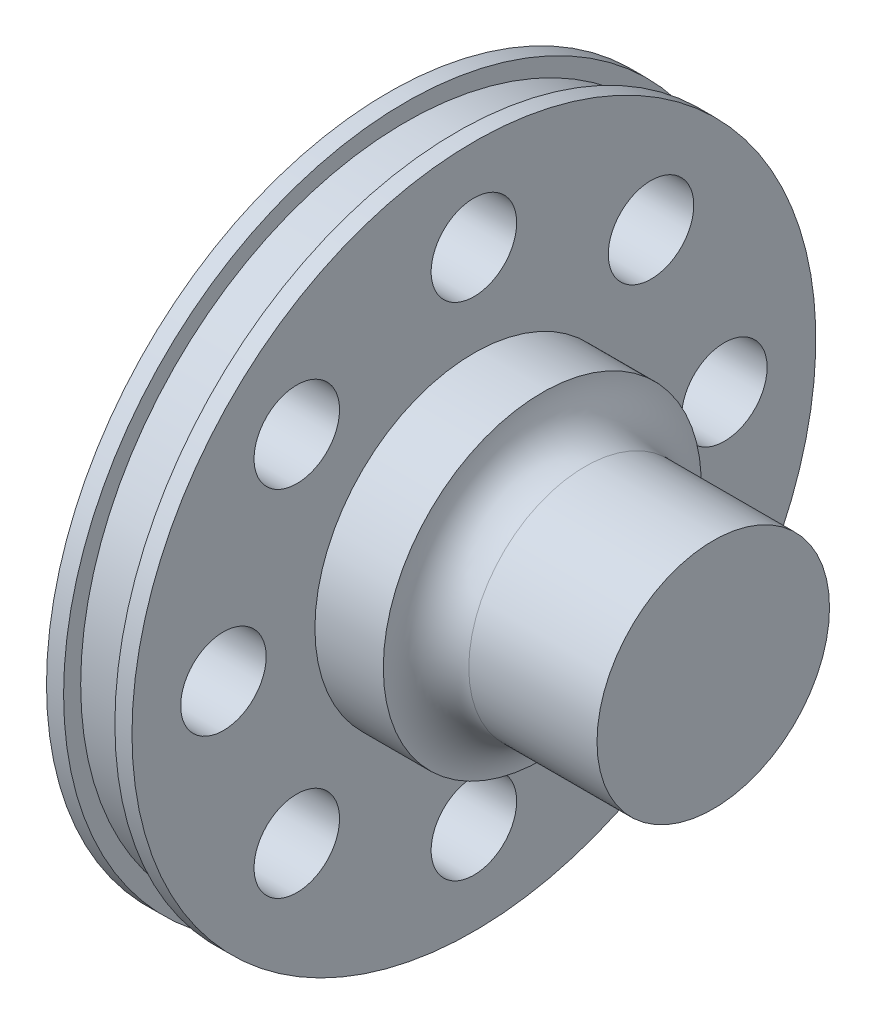
SolidWorks part; units mm, degrees
ref_plane "Front Plane" through (0, 0, 0) normal (0, 0, 1) x (1, 0, 0)
ref_plane "Top Plane" through (0, 0, 0) normal (0, 1, 0) x (1, 0, 0)
ref_plane "Right Plane" through (0, 0, 0) normal (1, 0, 0) x (0, 0, -1)
sketch "Sketch2" plane through (0, 0, 0) normal (0, 0, 1) x (1, 0, 0)
  line L0 (-1001.1848, 0) -> (0, 0) construction
  line L1 (45.72, 17.272) -> (20.32, 17.272)
  line L2 (45.72, 17.272) -> (45.72, 0)
  line L3 (20.32, 17.272) -> (20.32, 23.622)
  line L4 (20.32, 23.622) -> (10.16, 23.622)
  line L5 (10.16, 23.622) -> (10.16, 50.8)
  line L6 (10.16, 50.8) -> (7.62, 50.8)
  line L8 (0, 0) -> (45.72, 0)
  line L9 (0, 50.8) -> (-2.54, 50.8)
  line L11 (0, 50.8) -> (0, 48.26)
  line L12 (0, 48.26) -> (7.62, 48.26)
  line L13 (7.62, 50.8) -> (7.62, 48.26)
  line L14 (-2.54, 12.7) -> (0, 12.7)
  line L15 (0, 12.7) -> (0, 0)
  line L16 (0, 0) -> (1005.8009, 0) construction
  line L20 (-2.54, 50.8) -> (-2.54, 12.7)
  dimension "D1" = 17.272
  dimension "D2" = 6.35
  dimension "D3" = 25.4
  dimension "D4" = 45.72
  dimension "D5" = 12.7
  dimension "D6" = 50.8
  dimension "D7" = 7.62
  dimension "D8" = 2.54
  dimension "D9" = 2.54
  dimension "D10" = 2.54
  dimension "D11" = 12.7
revolve "Revolve1" add sketch "Sketch2" angle 360 about L0
sketch "Sketch3" plane through (10.16, 0, 0) normal (1, 0, 0) x (0, 0, -1)
  line L0 (-109.3795, 0) -> (-123.8259, 0) construction
  line L1 (0, -92.5704) -> (0, -109.6196) construction
  circle A50 centre (26.3122, 26.3122) radius 6.35
  circle A51 centre (0, 37.211) radius 6.35
  circle A52 centre (37.211, 0) radius 6.35
  circle A53 centre (26.3122, -26.3122) radius 6.35
  circle A54 centre (0, -37.211) radius 6.35
  circle A55 centre (-26.3122, -26.3122) radius 6.35
  circle A56 centre (-37.211, 0) radius 6.35
  circle A57 centre (-26.3122, 26.3122) radius 6.35
  dimension "D1" = 37.211
  dimension "D2" = 12.7
extrude "Cut-Extrude1" cut sketch "Sketch3" against normal through all
fillet "Fillet1" radius 6.35 1 edges at (20.32, 0, 17.272)
